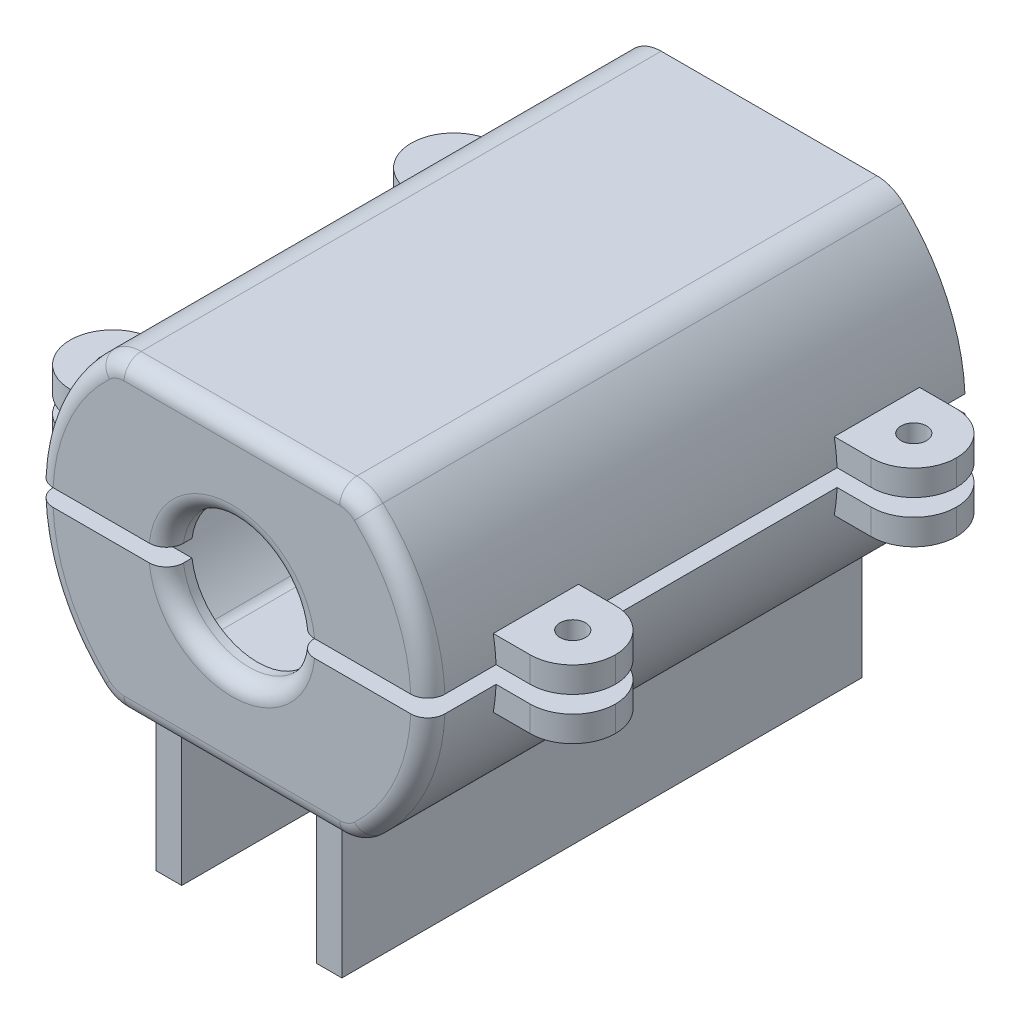
SolidWorks part; units mm, degrees
ref_plane "Front Plane" through (0, 0, 0) normal (0, 0, 1) x (1, 0, 0)
ref_plane "Top Plane" through (0, 0, 0) normal (0, 1, 0) x (1, 0, 0)
ref_plane "Right Plane" through (0, 0, 0) normal (1, 0, 0) x (0, 0, -1)
sketch "Sketch1" plane through (0, 0, 0) normal (0, 0, 1) x (1, 0, 0)
  line L0 (-12.6491, -14.5) -> (12.6491, -14.5) construction
  line L1 (12.6491, 14.5) -> (-12.6491, 14.5) construction
  line L2 (-12.6491, -14.5) -> (12.6491, -14.5)
  line L3 (12.6491, 14.5) -> (-12.6491, 14.5)
  line L4 (12.6491, 15) -> (-12.6491, 15)
  line L5 (-12.6491, -15) -> (12.6491, -15)
  line L6 (-12.6491, -18) -> (12.6491, -18)
  line L7 (12.6491, 18) -> (-12.6491, 18)
  arc A0 (12.6491, -14.5) -> (13.3328, -14.2297) centre (12.6491, -13.5) ccw construction
  arc A1 (-13.3328, -14.2297) -> (-12.6491, -14.5) centre (-12.6491, -13.5) ccw construction
  arc A2 (-13.3328, 14.2297) -> (-13.3328, -14.2297) centre (0, 0) ccw construction
  arc A3 (-12.6491, 14.5) -> (-13.3328, 14.2297) centre (-12.6491, 13.5) ccw construction
  arc A4 (13.3328, 14.2297) -> (12.6491, 14.5) centre (12.6491, 13.5) ccw construction
  arc A5 (13.3328, -14.2297) -> (13.3328, 14.2297) centre (0, 0) ccw construction
  arc A6 (12.6491, -14.5) -> (13.3328, -14.2297) centre (12.6491, -13.5) ccw
  arc A7 (-13.3328, -14.2297) -> (-12.6491, -14.5) centre (-12.6491, -13.5) ccw
  arc A8 (-13.3328, 14.2297) -> (-13.3328, -14.2297) centre (0, 0) ccw
  arc A9 (-12.6491, 14.5) -> (-13.3328, 14.2297) centre (-12.6491, 13.5) ccw
  arc A10 (13.3328, 14.2297) -> (12.6491, 14.5) centre (12.6491, 13.5) ccw
  arc A11 (13.3328, -14.2297) -> (13.3328, 14.2297) centre (0, 0) ccw
  arc A12 (13.6747, -14.5946) -> (13.6747, 14.5946) centre (0, 0) ccw
  arc A13 (13.6747, 14.5946) -> (12.6491, 15) centre (12.6491, 13.5) ccw
  arc A14 (-12.6491, 15) -> (-13.6747, 14.5946) centre (-12.6491, 13.5) ccw
  arc A15 (-13.6747, 14.5946) -> (-13.6747, -14.5946) centre (0, 0) ccw
  arc A16 (-13.6747, -14.5946) -> (-12.6491, -15) centre (-12.6491, -13.5) ccw
  arc A17 (12.6491, -15) -> (13.6747, -14.5946) centre (12.6491, -13.5) ccw
  arc A18 (-15.7259, 16.7838) -> (-15.7259, -16.7838) centre (0, 0) ccw
  arc A19 (-15.7259, -16.7838) -> (-12.6491, -18) centre (-12.6491, -13.5) ccw
  arc A20 (12.6491, -18) -> (15.7259, -16.7838) centre (12.6491, -13.5) ccw
  arc A21 (15.7259, -16.7838) -> (15.7259, 16.7838) centre (0, 0) ccw
  arc A22 (15.7259, 16.7838) -> (12.6491, 18) centre (12.6491, 13.5) ccw
  arc A23 (-12.6491, 18) -> (-15.7259, 16.7838) centre (-12.6491, 13.5) ccw
  dimension "D1" = 0.5
  dimension "D2" = 3
extrude "Boss-Extrude1" add sketch "Sketch1" against normal blind 60 contours L7 A23 A18 A19 L6 A20 A21 A22 A17 L5 A16 A15 A14 L4 A13 A12 region at (-14.0886, -17.1417, 0)
sketch "Sketch2" plane through (0, 0, 0) normal (0, 0, 1) x (1, 0, 0)
  line L2 (12.6491, 18) -> (-12.6491, 18)
  line L3 (-12.6491, -18) -> (12.6491, -18)
  line L4 (12.6491, 18) -> (-12.6491, 18)
  line L5 (-12.6491, -18) -> (12.6491, -18)
  circle A0 centre (0, 0) radius 6.75 construction
  circle A1 centre (0, 0) radius 6.75
  circle A2 centre (0, 0) radius 7.75
  arc A6 (-12.6491, 18) -> (-15.7259, 16.7838) centre (-12.6491, 13.5) ccw
  arc A7 (-15.7259, 16.7838) -> (-15.7259, -16.7838) centre (0, 0) ccw
  arc A8 (-15.7259, -16.7838) -> (-12.6491, -18) centre (-12.6491, -13.5) ccw
  arc A9 (12.6491, -18) -> (15.7259, -16.7838) centre (12.6491, -13.5) ccw
  arc A10 (15.7259, -16.7838) -> (15.7259, 16.7838) centre (0, 0) ccw
  arc A11 (15.7259, 16.7838) -> (12.6491, 18) centre (12.6491, 13.5) ccw
  arc A12 (-12.6491, 18) -> (-15.7259, 16.7838) centre (-12.6491, 13.5) ccw
  arc A13 (-15.7259, 16.7838) -> (-15.7259, -16.7838) centre (0, 0) ccw
  arc A14 (-15.7259, -16.7838) -> (-12.6491, -18) centre (-12.6491, -13.5) ccw
  arc A15 (12.6491, -18) -> (15.7259, -16.7838) centre (12.6491, -13.5) ccw
  arc A16 (15.7259, -16.7838) -> (15.7259, 16.7838) centre (0, 0) ccw
  arc A17 (15.7259, 16.7838) -> (12.6491, 18) centre (12.6491, 13.5) ccw
  arc M9 (13.6747, -14.5946) -> (12.6491, -15) centre (12.6491, -13.5) cw
  line M10 (12.6491, -15) -> (-12.6491, -15)
  arc M11 (-12.6491, -15) -> (-13.6747, -14.5946) centre (-12.6491, -13.5) cw
  arc M12 (-13.6747, -14.5946) -> (-13.6747, 14.5946) centre (0, 0) cw
  arc M13 (-13.6747, 14.5946) -> (-12.6491, 15) centre (-12.6491, 13.5) cw
  line M14 (-12.6491, 15) -> (12.6491, 15)
  arc M15 (12.6491, 15) -> (13.6747, 14.5946) centre (12.6491, 13.5) cw
  arc M16 (13.6747, 14.5946) -> (13.6747, -14.5946) centre (0, 0) cw
  line M17 (12.6491, 18) -> (-12.6491, 18)
  arc M18 (-12.6491, 18) -> (-15.7259, 16.7838) centre (-12.6491, 13.5) ccw
  arc M19 (-15.7259, 16.7838) -> (-15.7259, -16.7838) centre (0, 0) ccw
  arc M20 (-15.7259, -16.7838) -> (-12.6491, -18) centre (-12.6491, -13.5) ccw
  line M21 (-12.6491, -18) -> (12.6491, -18)
  arc M22 (12.6491, -18) -> (15.7259, -16.7838) centre (12.6491, -13.5) ccw
  arc M23 (15.7259, -16.7838) -> (15.7259, 16.7838) centre (0, 0) ccw
  arc M24 (15.7259, 16.7838) -> (12.6491, 18) centre (12.6491, 13.5) ccw
  dimension "D2" = 1
  dimension "D1" = 0
extrude "Boss-Extrude2" add sketch "Sketch2" along normal blind 3 contours M24 M17 M18 M19 M20 M21 M22 M23 M16 M9 M10 M11 M12 M13 M14 M15 | A2 M9 M16 M15 M14 M13 M12 M11 M10 region at (14.0886, 17.1417, 0) region at (13.0167, -14.43, 0)
sketch "Sketch3" plane through (0, 0, 3) normal (0, 0, 1) x (1, 0, 0)
  circle A0 centre (0, 0) radius 7.75 construction
  circle A1 centre (0, 0) radius 7.75
  circle A2 centre (0, 0) radius 10.75
  dimension "D1" = 3
extrude "Boss-Extrude3" [suppressed] add sketch "Sketch3" along normal blind 6
sketch "Sketch4" [suppressed] plane through (0, 0, 9) normal (0, 0, 1) x (1, 0, 0)
  circle A1 centre (0, 0) radius 10.75
  circle A2 centre (0, 0) radius 10.75
  dimension "D1" = 0
extrude "Boss-Extrude4" [suppressed] add sketch "Sketch4" along normal blind 1
dome "Dome1" [suppressed] faces to dome 1 distance 4 parameters "D1"=4
fillet "Fillet1" radius 2 9 edges at (23, 0, 3) (14.3033, -17.6849, 3) (0, -18, 3) (-14.3033, -17.6849, 3) (-23, 0, 3) (-14.3033, 17.6849, 3) (0, 18, 3) (14.3033, 17.6849, 3) (7.75, 0, 3)
sketch "Sketch5" plane through (0, 0, 3) normal (0, 0, 1) x (1, 0, 0)
  line L1 (-27.5, -1) -> (27.5, -1)
  line L2 (-27.5, -1) -> (-27.5, 1)
  line L3 (-27.5, 1) -> (27.5, 1)
  line L4 (27.5, -1) -> (27.5, 1)
  line L5 (-27.5, -1) -> (27.5, 1) construction
  line L6 (-27.5, 1) -> (27.5, -1) construction
  point P0 (0, 0)
  dimension "D1" = 2
  dimension "D2" = 55
extrude "Cut-Extrude1" cut sketch "Sketch5" against normal through all both and the other way through all
sketch "Sketch6" plane through (0, -18, 0) normal (0, -1, 0) x (1, 0, 0)
  line L0 (12.6491, 1) -> (-12.6491, 1) construction
  line L1 (-7.8925, 1) -> (7.8925, 1) construction
  line L2 (-7.8925, 1) -> (-7.8925, -60) construction
  line L3 (-7.8925, -60) -> (7.8925, -60) construction
  line L4 (7.8925, 1) -> (7.8925, -60) construction
  line L5 (-12.6491, -60) -> (12.6491, -60) construction
  line L7 (-7.8925, 1) -> (-10.8925, 1)
  line L8 (-7.8925, 1) -> (-7.8925, -60)
  line L9 (-7.8925, -60) -> (-10.8925, -60)
  line L10 (-10.8925, 1) -> (-10.8925, -60)
  line L11 (7.8925, -60) -> (10.8925, -60)
  line L12 (7.8925, -60) -> (7.8925, 1)
  line L13 (7.8925, 1) -> (10.8925, 1)
  line L14 (10.8925, -60) -> (10.8925, 1)
  point P8 (0, 1)
  dimension "D1" = 15.785
  dimension "D2" = 3
  dimension "D3" = 3
extrude "Boss-Extrude5" add sketch "Sketch6" along normal blind 15.875
sketch "Sketch7" plane through (0, 0, 0) normal (0, 1, 0) x (1, 0, 0)
  line L0 (-19.975, 60) -> (-19.975, 0) construction
  line L1 (-19.975, 55) -> (-31.975, 55)
  line L2 (-19.975, 55) -> (-19.975, 45)
  line L3 (-19.975, 45) -> (-31.975, 45)
  line L4 (-31.975, 55) -> (-31.975, 45)
  line L5 (-22.9783, 60) -> (-19.975, 60) construction
  line L6 (-19.975, 5) -> (-31.975, 5)
  line L7 (-19.975, 15) -> (-19.975, 5)
  line L8 (-19.975, 15) -> (-31.975, 15)
  line L9 (-31.975, 15) -> (-31.975, 5)
  line L10 (0, -28.5312) -> (0, 28.5312) construction
  line L11 (31.975, 15) -> (31.975, 5)
  line L12 (19.975, 15) -> (31.975, 15)
  line L13 (19.975, 15) -> (19.975, 5)
  line L14 (19.975, 5) -> (31.975, 5)
  line L15 (31.975, 55) -> (31.975, 45)
  line L16 (19.975, 45) -> (31.975, 45)
  line L17 (19.975, 55) -> (19.975, 45)
  line L18 (19.975, 55) -> (31.975, 55)
  dimension "D1" = 12
  dimension "D2" = 10
  dimension "D3" = 5
  dimension "D5" = 30
  dimension "D4" = 2
extrude "Boss-Extrude6" add sketch "Sketch7" along normal blind 3 from surface starting at face at (-16.5178, 1, -14.5708)
extrude "Boss-Extrude7" add sketch "Sketch7<2>" against normal blind 3 from surface starting at face at (-16.5066, -1, -14.6303)
sketch "Sketch7<2>" plane through (0, 0, 0) normal (0, 1, 0) x (1, 0, 0) same geometry as "Sketch7"
fillet "Fillet2" radius 5 8 edges at (31.975, 2.5, -45) (31.975, 2.5, -55) (31.975, 2.5, -15) (31.975, 2.5, -5) (-31.975, 2.5, -15) (-31.975, 2.5, -5) (-31.975, 2.5, -55) (-31.975, 2.5, -45)
fillet "Fillet3" radius 5 8 edges at (31.975, -2.5, -55) (31.975, -2.5, -45) (31.975, -2.5, -15) (31.975, -2.5, -5) (-31.975, -2.5, -5) (-31.975, -2.5, -15) (-31.975, -2.5, -45) (-31.975, -2.5, -55)
sketch "Sketch8" plane through (0, 4, 0) normal (0, 1, 0) x (1, 0, 0)
  circle A0 centre (-26.975, 50) radius 1.5
  circle A1 centre (-26.975, 10) radius 1.5
  arc A3 (-31.975, 10) -> (-26.975, 5) centre (-26.975, 10) ccw construction
  circle A4 centre (26.975, 10) radius 1.5
  arc A5 (31.975, 10) -> (26.975, 15) centre (26.975, 10) ccw construction
  circle A6 centre (26.975, 50) radius 1.5
  arc A7 (26.975, 45) -> (31.975, 50) centre (26.975, 50) ccw construction
  point P8 (-26.975, 10.2109)
  point P9 (0, 0)
  point P17 (0, 0)
  dimension "D1" = 3
  dimension "D2" = 3
  dimension "D3" = 3
  dimension "D4" = 3
extrude "Cut-Extrude2" cut sketch "Sketch8" against normal blind 13
